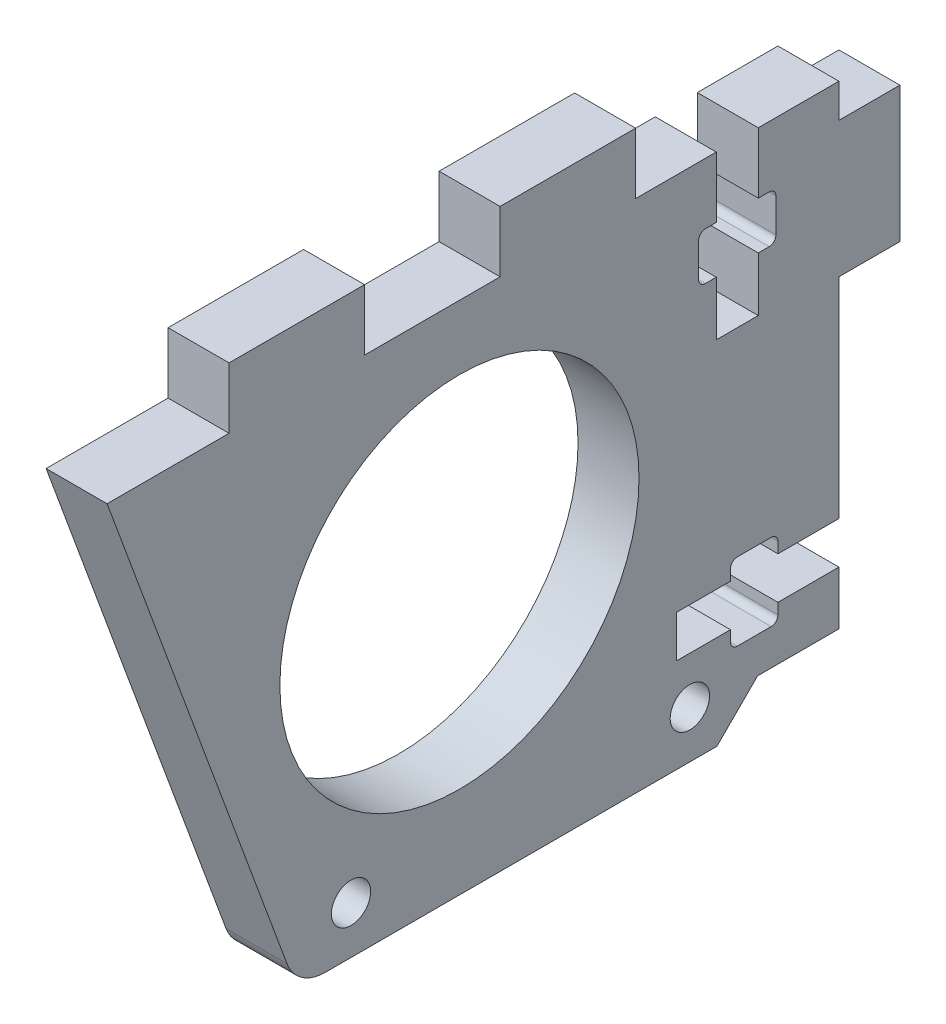
SolidWorks part; units mm, degrees
ref_plane "Front Plane" through (0, 0, 0) normal (0, 0, 1) x (1, 0, 0)
ref_plane "Top Plane" through (0, 0, 0) normal (0, 1, 0) x (1, 0, 0)
ref_plane "Right Plane" through (0, 0, 0) normal (1, 0, 0) x (0, 0, -1)
sketch "Sketch1" plane through (0, 0, 0) normal (1, 0, 0) x (0, 0, -1)
  line L0 (0, 0) -> (0, -35)
  line L1 (0, -35) -> (-54, 0)
  line L2 (-54, 0) -> (0, 0)
  dimension "D1" = 35
  dimension "D2" = 54
extrude "Boss-Extrude1" add sketch "Sketch1" along normal blind 4.5
sketch "Sketch2" plane through (4.5, 0, 0) normal (1, 0, 0) x (0, 0, -1)
  line L0 (0, -35) -> (0, 0) construction
  line L1 (-4.5, -2.5) -> (4.5, -2.5)
  line L2 (-4.5, -2.5) -> (-4.5, -12.5)
  line L3 (-4.5, -12.5) -> (4.5, -12.5)
  line L4 (4.5, -2.5) -> (4.5, -12.5)
  line L5 (-4.5, -2.5) -> (4.5, -12.5) construction
  line L6 (-4.5, -12.5) -> (4.5, -2.5) construction
  line L7 (0, 0) -> (-54, 0) construction
  point P0 (0, -7.5)
  dimension "D1" = 10
  dimension "D2" = 7.5
  dimension "D3" = 4.5
extrude "Boss-Extrude2" add sketch "Sketch2" against normal through all
sketch "Sketch3" plane through (4.5, 0, 0) normal (1, 0, 0) x (0, 0, -1)
  line L0 (0, -35) -> (-15, -35)
  line L1 (0, -25) -> (-54, 0)
  line L4 (0, -35) -> (0, -12.5) construction
  line L5 (0, -25) -> (0, -35)
  line L6 (-54, 0) -> (-15, -35)
  dimension "D1" = 15
  dimension "D2" = 10
extrude "Boss-Extrude3" add sketch "Sketch3" against normal through all
sketch "Sketch4" plane through (4.5, 0, 0) normal (1, 0, 0) x (0, 0, -1)
  line L0 (0, -29.5) -> (-12, -29.5) construction
  line L1 (0, -35) -> (0, -12.5) construction
  line L2 (0, -27.95) -> (-12, -27.95) construction
  line L3 (-12, -27.95) -> (-12, -31.05) construction
  line L4 (0, -31.05) -> (0, -27.95)
  line L5 (0, -27.95) -> (-4.5, -27.95)
  line L6 (-4.5, -27.95) -> (-4.5, -27.15)
  line L7 (-5, -26.65) -> (-7.5, -26.65)
  line L8 (-8, -27.15) -> (-8, -27.95)
  line L9 (-8, -27.95) -> (-12, -27.95)
  line L10 (-12, -27.95) -> (-12, -31.05)
  line L12 (0, -31.05) -> (-12, -31.05) construction
  line L13 (-8, -31.05) -> (-12, -31.05)
  line L14 (-8, -31.85) -> (-8, -31.05)
  line L15 (-5, -32.35) -> (-7.5, -32.35)
  line L16 (-4.5, -31.05) -> (-4.5, -31.85)
  line L17 (0, -31.05) -> (-4.5, -31.05)
  line L18 (4.5, -12.5) -> (4.5, -2.5) construction
  line L19 (0, -18.5) -> (-33.3857, -18.5) construction
  line L20 (-54, 0) -> (-15, -35) construction
  line L37 (0, -31.05) -> (-12, -31.05) construction
  arc A0 (-8, -31.85) -> (-7.5, -32.35) centre (-7.5, -31.85) ccw
  arc A1 (-5, -32.35) -> (-4.5, -31.85) centre (-5, -31.85) ccw
  arc A2 (-4.5, -27.15) -> (-5, -26.65) centre (-5, -27.15) ccw
  arc A3 (-7.5, -26.65) -> (-8, -27.15) centre (-7.5, -27.15) ccw
  point P10 (4.5, -7.5)
  point P20 (-8, -32.35)
  point P23 (-4.5, -32.35)
  point P26 (-4.5, -26.65)
  point P29 (-8, -26.65)
  dimension "D7" = 0.5
  dimension "D1" = 12
  dimension "D2" = 1.55
  dimension "D3" = 2.85
  dimension "D4" = 3.5
  dimension "D5" = 8
  dimension "D6" = 22
extrude "Cut-Extrude1" cut sketch "Sketch4" against normal through all
sketch "Sketch5" plane through (4.5, 0, 0) normal (1, 0, 0) x (0, 0, -1)
  line L0 (0, 0) -> (-54, 0) construction
  line L1 (-25, 4.5) -> (-15, 4.5)
  line L2 (-25, 4.5) -> (-25, 0)
  line L3 (0, 0) -> (-54, 0) construction
  line L4 (-15, 4.5) -> (-15, 0)
  line L5 (-25, 4.5) -> (-20, 0) construction
  line L6 (-20, 0) -> (-15, 4.5) construction
  line L7 (-30, 0) -> (-30, 4.5) construction
  line L8 (-40, 0) -> (-45, 4.5) construction
  line L9 (-35, 4.5) -> (-40, 0) construction
  line L10 (-45, 4.5) -> (-45, 0)
  line L12 (-35, 4.5) -> (-35, 0)
  line L13 (-35, 4.5) -> (-45, 4.5)
  line L14 (-20, 0) -> (-15, 4.5) construction
  line L15 (-15, 0) -> (-25, 0)
  line L16 (-35, 0) -> (-45, 0)
  point P0 (-20, 0)
  point P14 (-40, 0)
  dimension "D3" = 4.5
  dimension "D1" = 20
  dimension "D2" = 10
  dimension "D4" = 20
  dimension "D5" = 5
extrude "Boss-Extrude4" add sketch "Sketch5" against normal through all
sketch "Sketch8" [suppressed] plane through (4.5, 0, 0) normal (1, 0, 0) x (0, 0, -1)
  line L0 (-15, -30) -> (-27, -30) construction
  line L1 (-15, -35) -> (-27, -35)
  line L2 (-15, -25) -> (-27, -25)
  line L3 (-15, -35) -> (0, -35) construction
  line L4 (-15, -25) -> (-15, -35)
  arc A1 (-27, -25) -> (-27, -35) centre (-27, -30) ccw
  dimension "D5" = 5
  dimension "D1" = 0
  dimension "D2" = 12
  dimension "D3" = 0
  dimension "D4" = 10
extrude "Boss-Extrude5" [suppressed] add sketch "Sketch8" against normal up to surface (4.5 mm away) up to face at (0, -17.3125, 11.9375)
sketch "Sketch9" [suppressed] plane through (4.5, 0, 0) normal (1, 0, 0) x (0, 0, -1)
  line L0 (-27, -30) -> (-22, -30) construction
  line L1 (-27, -27) -> (-22, -27)
  line L2 (-27, -33) -> (-22, -33)
  arc A0 (-27, -27) -> (-27, -33) centre (-27, -30) ccw
  arc A1 (-22, -33) -> (-22, -27) centre (-22, -30) ccw
  point P3 (-24.5, -30)
  dimension "D1" = 3
  dimension "D2" = 5
extrude "Cut-Extrude3" [suppressed] cut sketch "Sketch9" against normal through all
sketch "Sketch10" plane through (0, 0, 0) normal (-1, 0, 0) x (0, 0, 1)
  line L0 (15, -35) -> (54, -12)
  line L1 (54, -12) -> (54, 0)
  line L3 (54, 0) -> (15, -35)
  dimension "D1" = 12
extrude "Boss-Extrude6" [suppressed] add sketch "Sketch10" against normal through all
sketch "Sketch6" plane through (4.5, 0, 0) normal (1, 0, 0) x (0, 0, -1)
  line L0 (-30, 0) -> (-30, -11) construction
  line L1 (-25, 0) -> (-35, 0) construction
  line L2 (-28.45, -11) -> (-31.55, -11) construction
  line L3 (-31.55, -11) -> (-31.55, 0) construction
  line L4 (-28.45, 0) -> (-31.55, 0)
  line L5 (-31.55, 0) -> (-31.55, -4.5)
  line L6 (-31.55, -4.5) -> (-32.35, -4.5)
  line L7 (-32.85, -5) -> (-32.85, -7.5)
  line L8 (-32.35, -8) -> (-31.55, -8)
  line L9 (-31.55, -8) -> (-31.55, -11)
  line L10 (-31.55, -11) -> (-28.45, -11)
  line L11 (-28.45, -11) -> (-28.45, 0) construction
  line L12 (-28.45, -8) -> (-28.45, -11)
  line L13 (-27.65, -8) -> (-28.45, -8)
  line L14 (-27.15, -5) -> (-27.15, -7.5)
  line L15 (-28.45, -4.5) -> (-27.65, -4.5)
  line L16 (-28.45, 0) -> (-28.45, -4.5)
  arc A0 (-32.85, -7.5) -> (-32.35, -8) centre (-32.35, -7.5) ccw
  arc A1 (-32.35, -4.5) -> (-32.85, -5) centre (-32.35, -5) ccw
  arc A2 (-27.65, -4.5) -> (-27.15, -5) centre (-27.65, -5) cw
  arc A3 (-27.15, -7.5) -> (-27.65, -8) centre (-27.65, -7.5) cw
  point P12 (-32.85, -8)
  point P15 (-32.85, -4.5)
  point P26 (-27.15, -4.5)
  point P27 (-27.15, -8)
  dimension "D2" = 1.55
  dimension "D4" = 3.5
  dimension "D6" = 0.5
  dimension "D1" = 11
  dimension "D3" = 8
  dimension "D5" = 2.85
extrude "Cut-Extrude2" [suppressed] cut sketch "Sketch6" against normal through all
sketch "Sketch11" plane through (0, 0, 0) normal (-1, 0, 0) x (0, 0, 1)
  line L0 (7.5, 0) -> (7.5, -12) construction
  line L1 (0, 0) -> (15, 0) construction
  line L2 (5.95, -12) -> (9.05, -12)
  line L3 (9.05, -12) -> (9.05, -8)
  line L4 (9.05, -8) -> (9.85, -8)
  line L5 (10.35, -7.5) -> (10.35, -5)
  line L6 (9.85, -4.5) -> (9.05, -4.5)
  line L7 (9.05, -4.5) -> (9.05, 0)
  line L8 (9.05, 0) -> (5.95, 0)
  line L9 (9.05, -8) -> (9.05, -4.5) construction
  line L10 (0, 0) -> (15, 0) construction
  line L11 (5.95, -8) -> (5.95, -4.5) construction
  line L12 (5.95, -4.5) -> (5.95, 0)
  line L13 (5.15, -4.5) -> (5.95, -4.5)
  line L14 (4.65, -7.5) -> (4.65, -5)
  line L15 (5.95, -8) -> (5.15, -8)
  line L16 (5.95, -12) -> (5.95, -8)
  arc A0 (10.35, -5) -> (9.85, -4.5) centre (9.85, -5) ccw
  arc A1 (5.15, -4.5) -> (4.65, -5) centre (5.15, -5) ccw
  arc A2 (9.85, -8) -> (10.35, -7.5) centre (9.85, -7.5) ccw
  arc A3 (4.65, -7.5) -> (5.15, -8) centre (5.15, -7.5) ccw
  point P11 (7.5, 0)
  point P22 (10.35, -4.5)
  point P25 (4.65, -4.5)
  point P28 (10.35, -8)
  point P31 (4.65, -8)
  dimension "D7" = 0.5
  dimension "D1" = 12
  dimension "D3" = 2.85
  dimension "D8" = 0.5
  dimension "D2" = 3.5
  dimension "D4" = 8
  dimension "D5" = 1.55
  dimension "D6" = 0
extrude "Cut-Extrude4" cut sketch "Sketch11" against normal through all
sketch "Sketch12" plane through (0, 0, 0) normal (-1, 0, 0) x (0, 0, 1)
  line L0 (28, -18) -> (16, -6) construction
  line L1 (28, -18) -> (28, -4.75) construction
  line L2 (28, -18) -> (40, -6) construction
  line L3 (28, -18) -> (14.75, -18) construction
  line L4 (28, -18) -> (16, -30) construction
  line L5 (28, -18) -> (16, -6) construction
  line L6 (0, -27.95) -> (0, -12.5) construction
  line L7 (25, 0) -> (35, 0) construction
  circle A0 centre (28, -18) radius 13.25
  circle A1 centre (16, -6) radius 1.45
  circle A2 centre (40, -6) radius 1.45
  circle A3 centre (16, -30) radius 1.45
  dimension "D1" = 26.5
  dimension "D2" = 2.9
  dimension "D3" = 12
  dimension "D4" = 45
  dimension "D5" = 28
  dimension "D6" = 18
extrude "Cut-Extrude5" [suppressed] cut sketch "Sketch12" against normal through all
sketch "Sketch13" [suppressed] plane through (0, 0, 0) normal (-1, 0, 0) x (0, 0, 1)
  line L0 (38.894, -10.458) -> (43.005, -7.6119)
  line L1 (19.9513, -28.5252) -> (16.914, -32.497)
  line L6 (28, -18) -> (54, 0) construction
  line L7 (28, -18) -> (15, -35) construction
  arc A0 (19.9513, -28.5252) -> (38.894, -10.458) centre (28, -18) ccw
  arc A1 (16.914, -32.497) -> (43.005, -7.6119) centre (28, -18) ccw
  arc A3 (40.0595, -12.5107) -> (21.2428, -29.3975) centre (28, -18) ccw construction
  dimension "D1" = 5
extrude "Boss-Extrude7" [suppressed] add sketch "Sketch13" against normal through all
sketch "Sketch14" [suppressed] plane through (0, 0, 0) normal (-1, 0, 0) x (0, 0, 1)
  line L0 (28, -4.75) -> (28, -31.25) construction
  line L1 (28, -18) -> (40, -30) construction
  circle A0 centre (28, -18) radius 13.25 construction
  circle A1 centre (40, -30) radius 3.5
  dimension "D2" = 7
  dimension "D1" = 45
  dimension "D3" = 12
extrude "Boss-Extrude8" [suppressed] add sketch "Sketch14" against normal through all
sketch "Sketch15" [suppressed] plane through (0, 0, 0) normal (-1, 0, 0) x (0, 0, 1)
  line L0 (42.4749, -32.4749) -> (28, -18) construction
  arc A0 (38.305, -33.0622) -> (43.0622, -28.305) centre (40, -30) ccw construction
  circle A1 centre (40, -30) radius 1.55
  dimension "D1" = 2.9
extrude "Cut-Extrude6" [suppressed] cut sketch "Sketch15" against normal through all
sketch "Sketch16" plane through (4.5, 0, 0) normal (1, 0, 0) x (0, 0, -1)
  line L0 (0, -34.5) -> (-39, -34.5) construction
  line L1 (0, -27.95) -> (0, -12.5) construction
  line L2 (-15, -34.5) -> (-39, -34.5) construction
  line L3 (-15, -38.5) -> (-39, -38.5)
  line L4 (-15, -30.5) -> (-39, -30.5)
  arc A0 (-15, -38.5) -> (-15, -30.5) centre (-15, -34.5) ccw
  arc A1 (-39, -30.5) -> (-39, -38.5) centre (-39, -34.5) ccw
  point P5 (-27, -34.5)
  point P12 (0, -20.225)
  dimension "D1" = 4
  dimension "D2" = 34.5
  dimension "D3" = 39
  dimension "D4" = 15
extrude "Boss-Extrude9" [suppressed] add sketch "Sketch16" against normal through all
sketch "Sketch17" [suppressed] plane through (4.5, 0, 0) normal (1, 0, 0) x (0, 0, -1)
  line L0 (-43, -34.5) -> (0, -34.5) construction
  line L1 (0, -27.75) -> (0, -12.5) construction
  line L2 (-26.5, -34.5) -> (-26.5, -20.0064) construction
  arc A0 (-42.1823, -32.0766) -> (-39, -38.5) centre (-39, -34.5) ccw construction
  circle A1 centre (-39, -34.5) radius 1.55
  circle A2 centre (-14, -34.5) radius 1.55
  dimension "D1" = 2.9
  dimension "D2" = 12.5
extrude "Cut-Extrude7" [suppressed] cut sketch "Sketch17" against normal through all
sketch "Sketch18" [suppressed] plane through (4.5, 0, 0) normal (1, 0, 0) x (0, 0, -1)
  line L0 (-15, -38.5) -> (0, -35)
  line L1 (0, -35) -> (-11.0314, -35)
  line L2 (-11.0314, -35) -> (-15, -38.5)
extrude "Boss-Extrude10" [suppressed] add sketch "Sketch18" against normal through all
sketch "Sketch20" plane through (4.5, 0, 0) normal (1, 0, 0) x (0, 0, -1)
  line L0 (0, -35) -> (0, -31.05) construction
  line L1 (-9, -38) -> (-37.9081, -38)
  line L2 (-40.7232, -36.0371) -> (-54, 0)
  line L3 (-54, 0) -> (-15, -35)
  line L4 (-15, -35) -> (-6, -35)
  line L5 (-9, -38) -> (-6, -35)
  line L6 (-40.7232, -36.0371) -> (-40, -38) construction
  line L7 (-40, -38) -> (-37.9081, -38) construction
  arc A1 (-37.9081, -38) -> (-40.7232, -36.0371) centre (-37.9081, -35) cw
  point P0 (0, -33.025)
  point P14 (-40, -38)
  dimension "D3" = 6
  dimension "D4" = 3
  dimension "D1" = 40
  dimension "D2" = 3
  dimension "D5" = 135
extrude "Boss-Extrude11" add sketch "Sketch20" against normal through all
sketch "Sketch21" plane through (4.5, 0, 0) normal (1, 0, 0) x (0, 0, -1)
  line L0 (0, -34.5) -> (-41.2895, -34.5) construction
  line L1 (0, -35) -> (0, -31.05) construction
  line L2 (-54, 0) -> (-40.7232, -36.0371) construction
  line L3 (0, -27.95) -> (0, -12.5) construction
  circle A0 centre (-36, -34.5) radius 1.45
  circle A1 centre (-11, -34.5) radius 1.45
  dimension "D2" = 2.9
  dimension "D3" = 2.9
  dimension "D1" = 25
  dimension "D4" = 34.5
  dimension "D5" = 11
extrude "Cut-Extrude8" cut sketch "Sketch21" against normal through all
sketch "Sketch22" plane through (4.5, 0, 0) normal (1, 0, 0) x (0, 0, -1)
  line L0 (0, -27.95) -> (0, -12.5) construction
  line L1 (-25, 0) -> (-35, 0) construction
  circle A0 centre (-28, -18) radius 13.25
  dimension "D2" = 18
  dimension "D3" = 26.5
  dimension "D1" = 28
extrude "Cut-Extrude9" cut sketch "Sketch22" against normal through all
equation "\"X-ROD-SPACING\"=45"
equation "\"Y-ROD-SPACING\"=75"
equation "\"Z-ROD-SPACING\"=17.5"
equation "\"Y-BED-OFFSET\"=2"
equation "\"Y-BED-ROD-INSET\"=3.5"
equation "\"Y-BED-SCREW-SPACING\"=209"
equation "\"Y-BED-SCREW-CUTOUT-SLOT-HEIGHT\"=2"
equation "\"T-SLOT-NUT-FILLET-RADIUS\"=0.5"
equation "\"T-SLOT-SCREW-SHAFT-RADIUS\"=1.55"
equation "\"T-SLOT-SCREW-SHAFT-CUTOUT-LENGTH\"=11.0"
equation "\"T-SLOT-NUT-DEPTH\"=3.5"
equation "\"T-SLOT-NUT-WIDTH\"=2.85"
equation "\"T-SLOT-NUT-END-DISTANCE\"=8"
equation "\"ACRYLIC-THICKNESS\"=10"
equation "\"ACRYLIC-THICKNESS2\"=4.5"
equation "\"ACRYLIC-TAB-CUTOUT-SIZE\"=\"ACRYLIC-THICKNESS\"+\"ACRYLIC-TAB-TOLERANCE\"*2"
equation "\"ACRYLIC-TAB-WIDTH\"=\"ACRYLIC-THICKNESS\""
equation "\"ACRYLIC-M3-HOLE\"=2.9"
equation "\"SMOOTHROD-CAP-SCREW-DISTANCE\"=20"
equation "\"FRAME-WIDTH-INNER\"=370"
equation "\"NEMA17-HOLE-SPACING\"=31"
equation "\"NEMA17-CENTRAL-CUTOUT\"=22.5"
equation "\"Z-BRACKET-REACH\"=55"
equation "\"Z-ROD-INSET\"=16"
equation "\"TOP-BRACKET-SPACING\"=40"
equation "\"SMOOTHROD-X-LENGTH\"=350"
equation "\"SMOOTHROD-Y-LENGTH\"=350"
equation "\"SMOOTHROD-Z-LENGTH\"=350"
equation "\"SMOOTHROD-TIGHTENING-HEADROOM\"=.25"
equation "\"LEADSCREW-Z-LENGTH\"=300"
equation "\"SCREW-LENGTH-FRAME\"=\"ACRYLIC-THICKNESS\" + 10"
equation "\"SCREW-LENGTH-MOTOR\"=\"ACRYLIC-THICKNESS\" + 5"
equation "\"SCREW-LENGTH-EXTRUDER\"=28"
equation "\"SCREW-HEAD-RADIUS\"=6"
equation "\"PRINTED-X-SMOOTHROD-DIAMETER\"=8.4"
equation "\"PRINTED-X-SMOOTHROD-CUTOUT\"=10"
equation "\"PRINTED-X-BASE-HEIGHT\"=10"
equation "\"PRINTED-LM8UU-CUTOUT-SIZE\"=15.5"
equation "\"PRINTED-LM8UU-CUTOUT-LENGTH\"=24.5"
equation "\"PRINTED-X-IDLER-HEIGHT\"=16"
equation "\"PSU-MOUNTING-WIDTH\"=95"
equation "\"PSU-MOUNTING-HEIGHT\"=177"
equation "\"Y-BELT-TO-ROD-DISTANCE\"=20"
equation "\"SPOOL-HOLDER-ROD-SPACING\"=150"
equation "\"ACRYLIC-X-CARRIAGE-WIDTH\"=55"
equation "\"ACRYLIC-X-CARRIAGE-HEIGHT\"=75"
equation "\"ACRYLIC-X-CARRIAGE-SCREW-SPACING-X\"=15"
equation "\"ACRYLIC-X-CARRIAGE-SCREW-SPACING-Y\"=33"
equation "\"ACRYLIC-X-CARRIAGE-CENTER-TAB-SPACING\"=14"
equation "\"ACRYLIC-X-CARRIAGE-EXTRUDER-SHELF-DEPTH\"=\"ACRYLIC-X-CARRIAGE-EXTRUDER-OFFSET\" + 28"
equation "\"D2@Sketch1\"=\"ACRYLIC-X-CARRIAGE-EXTRUDER-SHELF-DEPTH\""
equation "\"D1@Boss-Extrude1\"=\"ACRYLIC-THICKNESS2\""
equation "\"D1@Sketch2\"=\"ACRYLIC-TAB-WIDTH\""
equation "\"D3@Sketch2\"=\"ACRYLIC-THICKNESS2\""
equation "\"ACRYLIC-X-CARRIAGE-LM8UU-CUTOUT-WIDTH\"=24.25"
equation "\"ACRYLIC-X-CARRIAGE-EXTRUDER-BRACE-SPACING\"=23"
equation "\"ACRYLIC-X-CARRIAGE-EXTRUDER-BRACE-HEIGHT\"=35"
equation "\"D1@Sketch1\"=\"ACRYLIC-X-CARRIAGE-EXTRUDER-BRACE-HEIGHT\""
equation "\"D1@Sketch4\"=\"T-SLOT-SCREW-SHAFT-CUTOUT-LENGTH\"+1"
equation "\"D2@Sketch4\"=\"T-SLOT-SCREW-SHAFT-RADIUS\""
equation "\"D3@Sketch4\"=\"T-SLOT-NUT-WIDTH\""
equation "\"D4@Sketch4\"=\"T-SLOT-NUT-DEPTH\""
equation "\"D5@Sketch4\"=\"T-SLOT-NUT-END-DISTANCE\""
equation "\"D7@Sketch4\"=\"T-SLOT-NUT-FILLET-RADIUS\""
equation "\"ACRYLIC-X-CARRIAGE-EXTRUDER-BRACE-SCREW-SPACING\"=22"
equation "\"D6@Sketch4\"=\"ACRYLIC-X-CARRIAGE-EXTRUDER-BRACE-SCREW-SPACING\""
equation "\"ACRYLIC-X-CARRIAGE-EXTRUDER-BRACE-TAB-OFFSET\"=20"
equation "\"D1@Sketch5\"=\"ACRYLIC-X-CARRIAGE-EXTRUDER-BRACE-TAB-OFFSET\""
equation "\"D2@Sketch5\"=\"ACRYLIC-TAB-WIDTH\""
equation "\"D3@Sketch5\"=\"ACRYLIC-THICKNESS2\""
equation "\"ACRYLIC-X-CARRIAGE-EXTRUDER-OFFSET\"=26"
equation "\"ACRYLIC-X-CARRIAGE-EXTRUDER-ANGLE\"=90"
equation "\"D1@Sketch6\"=\"T-SLOT-SCREW-SHAFT-CUTOUT-LENGTH\""
equation "\"D2@Sketch6\"=\"T-SLOT-SCREW-SHAFT-RADIUS\""
equation "\"D3@Sketch6\"=\"T-SLOT-NUT-END-DISTANCE\""
equation "\"D4@Sketch6\"=\"T-SLOT-NUT-DEPTH\""
equation "\"D5@Sketch6\"=\"T-SLOT-NUT-WIDTH\""
equation "\"D6@Sketch6\"=\"T-SLOT-NUT-FILLET-RADIUS\""
equation "\"D1@Sketch11\"=\"T-SLOT-SCREW-SHAFT-CUTOUT-LENGTH\"+1"
equation "\"D2@Sketch11\"=\"T-SLOT-NUT-DEPTH\""
equation "\"D3@Sketch11\"=\"T-SLOT-NUT-WIDTH\""
equation "\"D4@Sketch11\"=\"T-SLOT-NUT-END-DISTANCE\""
equation "\"D5@Sketch11\"=\"T-SLOT-SCREW-SHAFT-RADIUS\""
equation "\"D7@Sketch11\"=\"T-SLOT-NUT-FILLET-RADIUS\""
equation "\"D8@Sketch11\"=\"T-SLOT-NUT-FILLET-RADIUS\""
equation "\"D2@Sketch12\"=\"ACRYLIC-M3-HOLE\""
equation "\"D1@Sketch15\"=\"ACRYLIC-M3-HOLE\""
equation "\"D1@Sketch17\"=\"ACRYLIC-M3-HOLE\""
equation "\"D2@Sketch21\"=\"ACRYLIC-M3-HOLE\""
equation "\"D3@Sketch21\"=\"ACRYLIC-M3-HOLE\""
